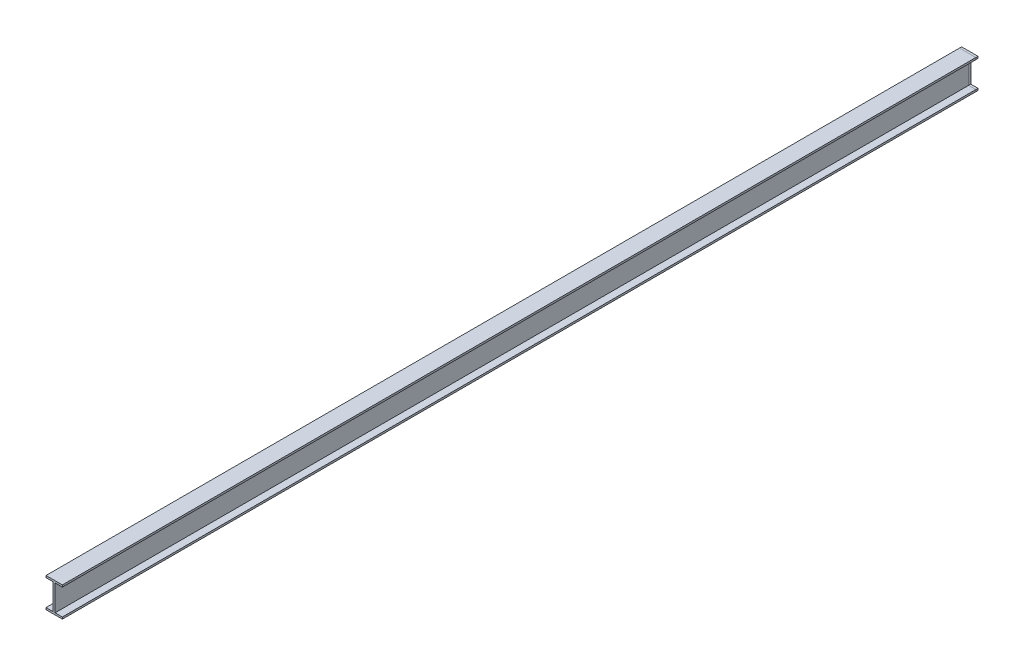
SolidWorks part; units mm, degrees
ref_plane "Front Plane" through (0, 0, 0) normal (0, 0, 1) x (1, 0, 0)
ref_plane "Top Plane" through (0, 0, 0) normal (0, 1, 0) x (1, 0, 0)
ref_plane "Right Plane" through (0, 0, 0) normal (1, 0, 0) x (0, 0, -1)
sketch "Sketch2" plane through (0, 0, 0) normal (0, 0, 1) x (1, 0, 0)
  line L0 (0, 177.8) -> (0, 0) construction
  line L1 (-49.022, 0) -> (49.022, 0)
  line L2 (0, 0) -> (0, 11.43)
  line L3 (-49.022, 11.43) -> (49.022, 11.43)
  line L4 (49.022, 0) -> (49.022, 11.43)
  line L5 (0, 11.43) -> (5.715, 11.43)
  line L6 (0, 11.43) -> (0, 166.37)
  line L7 (0, 166.37) -> (5.715, 166.37)
  line L8 (5.715, 11.43) -> (5.715, 166.37)
  line L9 (-49.022, 166.37) -> (49.022, 166.37)
  line L10 (0, 166.37) -> (0, 177.8)
  line L11 (-49.022, 177.8) -> (49.022, 177.8)
  line L12 (49.022, 166.37) -> (49.022, 177.8)
  line L13 (-49.022, 0) -> (-49.022, 11.43)
  line L14 (-5.715, 11.43) -> (-5.715, 166.37)
  line L15 (-49.022, 166.37) -> (-49.022, 177.8)
  dimension "D1" = 177.8
  dimension "D2" = 11.43
  dimension "D3" = 11.43
  dimension "D4" = 5.715
  dimension "D5" = 49.022
  dimension "D6" = 49.022
extrude "Boss-Extrude1" add sketch "Sketch2" along normal blind 5486.4 contours L15 L9 L10 L11 | L9 L12 L11 L10 L7 | L3 L8 L7 L6 | L14 L3 L6 L9 | L13 L1 L2 L3 | L1 L4 L3 L2 region at (-24.511, 5.715, 0) region at (24.511, 5.715, 0) region at (2.8575, 88.9, 0) region at (-2.8575, 88.9, 0) region at (24.511, 172.085, 0) region at (-24.511, 172.085, 0)
ref_plane "Plane1" through (0, 0, 12.7) normal (0, 0, 1) x (1, 0, 0)
split line "Split Line1"
